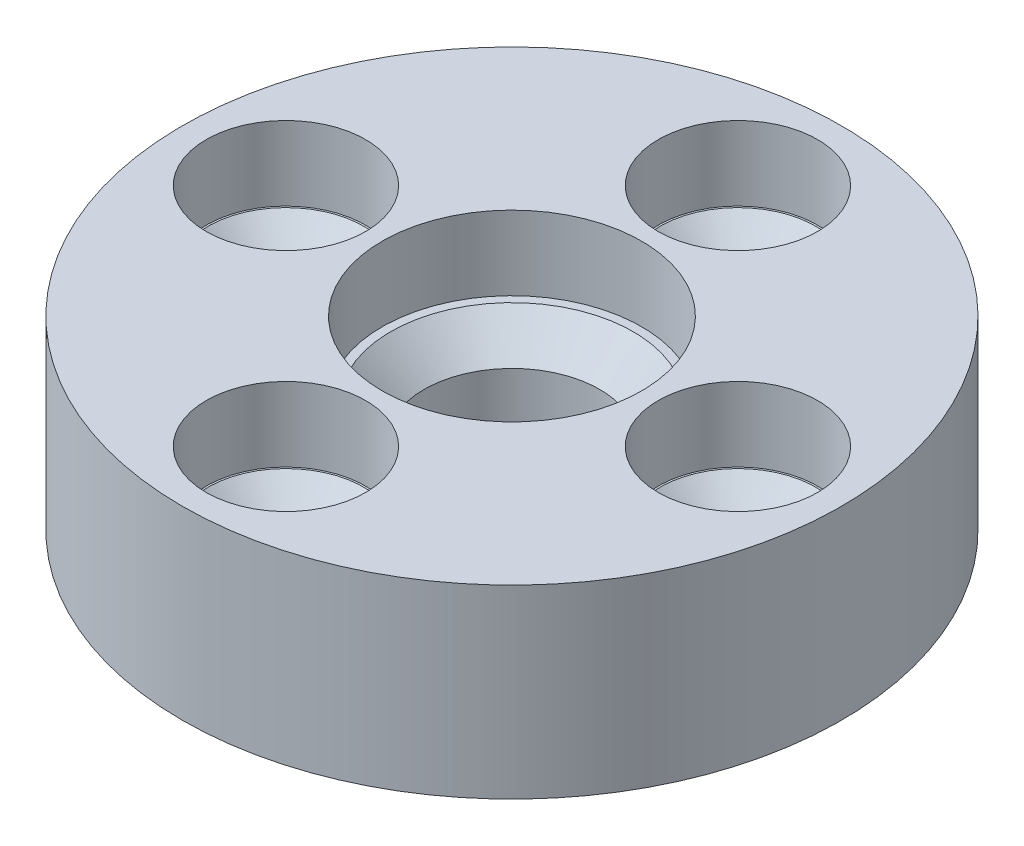
SolidWorks part; units mm, degrees
ref_plane "Front Plane" through (0, 0, 0) normal (0, 0, 1) x (1, 0, 0)
ref_plane "Top Plane" through (0, 0, 0) normal (0, 1, 0) x (1, 0, 0)
ref_plane "Right Plane" through (0, 0, 0) normal (1, 0, 0) x (0, 0, -1)
ref_axis "Axis1" through (-6.6339, 0, 0) along (1, 0, 0)
sketch "Sketch1" plane through (0, 0, 0) normal (0, 1, 0) x (1, 0, 0)
  circle A0 centre (0, 0) radius 8.89
  circle A1 centre (0, 0) radius 6.096 construction
  circle A2 centre (6.096, 0) radius 1.2
  circle A3 centre (0, 6.096) radius 1.2
  circle A4 centre (-6.096, 0) radius 1.2
  circle A5 centre (0, -6.096) radius 1.2
  circle A6 centre (0, 0) radius 2.3713
  point P14 (0, 0)
  dimension "D1" = 17.78
  dimension "D2" = 12.192
  dimension "D3" = 2.4
  dimension "D5" = 4.7425
  dimension "D4" = 4
extrude "Boss-Extrude1" add sketch "Sketch1" along normal blind 5 contours A0 A6 A5 A4 A3 A2 region at (-8.6386, 0, 0)
sketch "Sketch2" plane through (0, 5, 0) normal (0, 1, 0) x (1, 0, 0)
  circle A0 centre (0, 6.096) radius 2.15
  circle A1 centre (-6.096, 0) radius 2.15
  circle A2 centre (6.096, 0) radius 2.15
  circle A3 centre (0, -6.096) radius 2.15
  circle A4 centre (0, 0) radius 3.5
  dimension "D1" = 4.3
  dimension "D2" = 7
extrude "Cut-Extrude1" cut sketch "Sketch2" against normal blind 2
chamfer "Chamfer1" distance 0.9 angle 45 5 edges at (0, 3, 7.296) (6.096, 3, 1.2) (0, 3, 2.3713) (-6.096, 3, 1.2) (0, 3, -4.896)
